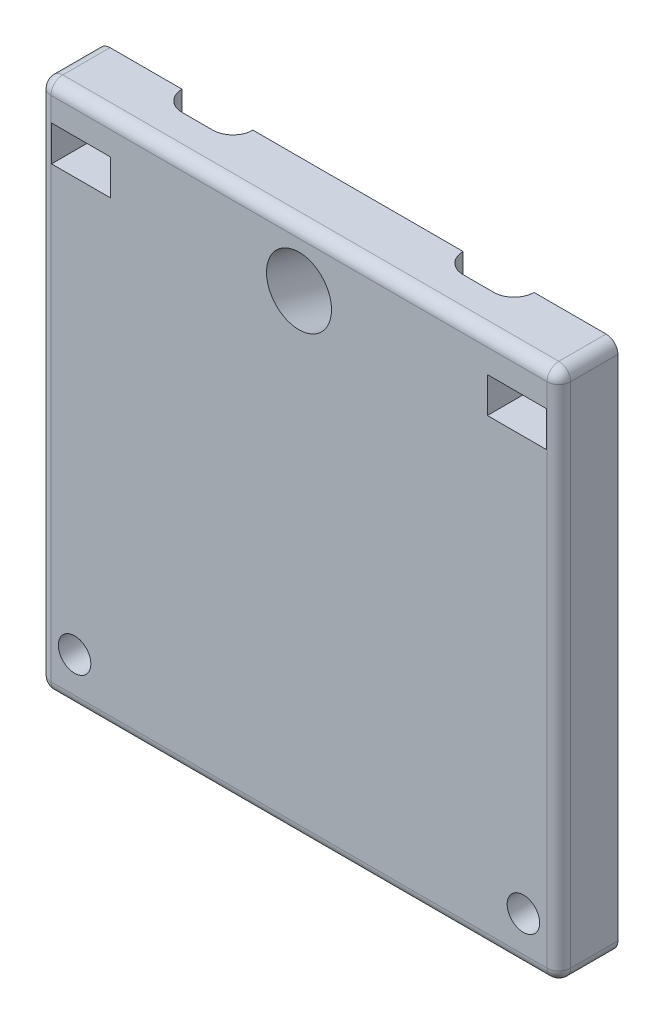
SolidWorks part; units mm, degrees
ref_plane "Front Plane" through (0, 0, 0) normal (0, 0, 1) x (1, 0, 0)
ref_plane "Top Plane" through (0, 0, 0) normal (0, 1, 0) x (1, 0, 0)
ref_plane "Right Plane" through (0, 0, 0) normal (1, 0, 0) x (0, 0, -1)
sketch "Sketch1" plane through (0, 0, 0) normal (0, 0, 1) x (1, 0, 0)
  line L1 (-22, 22.5) -> (22, 22.5)
  line L2 (-22, 22.5) -> (-22, -22.5)
  line L3 (-22, -22.5) -> (22, -22.5)
  line L4 (22, 22.5) -> (22, -22.5)
  line L5 (-22, 22.5) -> (22, -22.5) construction
  line L6 (-22, -22.5) -> (22, 22.5) construction
  point P0 (0, 0)
  dimension "D1" = 44
  dimension "D2" = 45
extrude "Base" add sketch "Sketch1" along normal blind 5
sketch "Sketch2" plane through (0, 22.5, 0) normal (0, 1, 0) x (1, 0, 0)
  line L0 (22, 0) -> (-22, 0) construction
  line L1 (-14.9, 0) -> (-8.9, 0)
  line L2 (0, 0) -> (0, -5) construction
  line L3 (22, -5) -> (-22, -5) construction
  line L5 (-14.9, 0) -> (-14.9, -5) construction
  line L6 (-13.2, -1.7) -> (-10.6, -1.7)
  line L7 (13.2, -1.7) -> (10.6, -1.7)
  line L8 (14.9, 0) -> (8.9, 0)
  arc A2 (-14.9, 0) -> (-13.2, -1.7) centre (-13.2, 0) ccw
  arc A3 (-10.6, -1.7) -> (-8.9, 0) centre (-10.6, 0) ccw
  arc A4 (14.9, 0) -> (13.2, -1.7) centre (13.2, 0) cw
  arc A5 (10.6, -1.7) -> (8.9, 0) centre (10.6, 0) cw
  point P0 (-11.9, 0)
  dimension "D1" = 6
  dimension "D2" = 11.9
  dimension "D3" = 1.7
extrude "Wire Grooves" cut sketch "Sketch2" against normal through all
sketch "Sketch4" plane through (0, 0, 0) normal (0, 0, -1) x (-1, 0, 0)
  line L0 (0, 22.5) -> (0, -22.5) construction
  line L3 (-22, 16.5291) -> (22, 16.5291) construction
  line L4 (-22, -22.5) -> (-22, 22.5) construction
  line L5 (22, 22.5) -> (22, -22.5) construction
  line L6 (-8.9, 22.5) -> (8.9, 22.5) construction
  line L8 (8.9, -22.5) -> (-8.9, -22.5) construction
  point P2 (0, 0)
  point P4 (0, 0)
  dimension "D1" = 5.9709
ref_plane "Screw Insertion Hole Reference" through (0, 1.1072, 4.1323) normal (0, -0.2588, -0.9659) x (-1, 0, 0)
sketch "Sketch3" plane through (0, 0.5961, 4.2692) normal (0, -0.2588, -0.9659) x (-1, 0, 0)
  line L0 (0, 0.5291) -> (0, 22.2625) construction
  line L2 (-8.9, 22.2625) -> (8.9, 22.2625) construction
  circle A0 centre (0, 16.2916) radius 2.75
  point P5 (0, 0)
  point P9 (0, 0)
  dimension "D1" = 5.5
  dimension "D2" = 5.9709
extrude "Screw Insertion Hole" cut sketch "Sketch3" against normal through all both and the other way through all
sketch "Sketch5" plane through (0, 0, 0) normal (0, 0, -1) x (-1, 0, 0)
  line L0 (-18.45, 22.5) -> (-18.45, -22.5) construction
  line L1 (-22, 22.5) -> (-14.9, 22.5) construction
  line L2 (-14.9, -22.5) -> (-22, -22.5) construction
  line L3 (0, 22.5) -> (0, -22.5) construction
  line L7 (-20.95, 19.5) -> (-15.95, 19.5)
  line L8 (-20.95, 19.5) -> (-20.95, 16.5)
  line L9 (-20.95, 16.5) -> (-15.95, 16.5)
  line L10 (-15.95, 19.5) -> (-15.95, 16.5)
  line L11 (-20.95, 19.5) -> (-15.95, 16.5) construction
  line L12 (-20.95, 16.5) -> (-15.95, 19.5) construction
  line L16 (-8.9, 22.5) -> (8.9, 22.5) construction
  line L17 (8.9, -22.5) -> (-8.9, -22.5) construction
  line L18 (20.95, 16.5) -> (15.95, 16.5)
  line L19 (15.95, 19.5) -> (15.95, 16.5)
  line L20 (20.95, 19.5) -> (15.95, 19.5)
  line L21 (20.95, 19.5) -> (20.95, 16.5)
  point P12 (-18.45, 18)
  dimension "D1" = 5
  dimension "D2" = 3
  dimension "D3" = 3
extrude "Zip Tie Slots" cut sketch "Sketch5" against normal through all
sketch "Sketch6" plane through (0, 0, 0) normal (0, 0, -1) x (-1, 0, 0)
  line L1 (-22, -22.5) -> (-22, 22.5) construction
  line L2 (-14.9, -22.5) -> (-22, -22.5) construction
  line L4 (0, 22.5) -> (0, -22.5) construction
  line L6 (-8.9, 22.5) -> (8.9, 22.5) construction
  line L7 (8.9, -22.5) -> (-8.9, -22.5) construction
  circle A0 centre (-19, -18.5) radius 1.375
  circle A2 centre (19, -18.5) radius 1.375
  dimension "D1" = 2.75
  dimension "D2" = 4
  dimension "D3" = 3
extrude "Mount Clamping Holes" cut sketch "Sketch6" against normal through all
fillet "Edge Fillets" radius 1 8 edges at (-22, 0, 5) (22, 0, 5) (0, -22.5, 5) (0, 22.5, 5) (22, 22.5, 2.5) (22, -22.5, 2.5) (-22, -22.5, 2.5) (-22, 22.5, 2.5)
